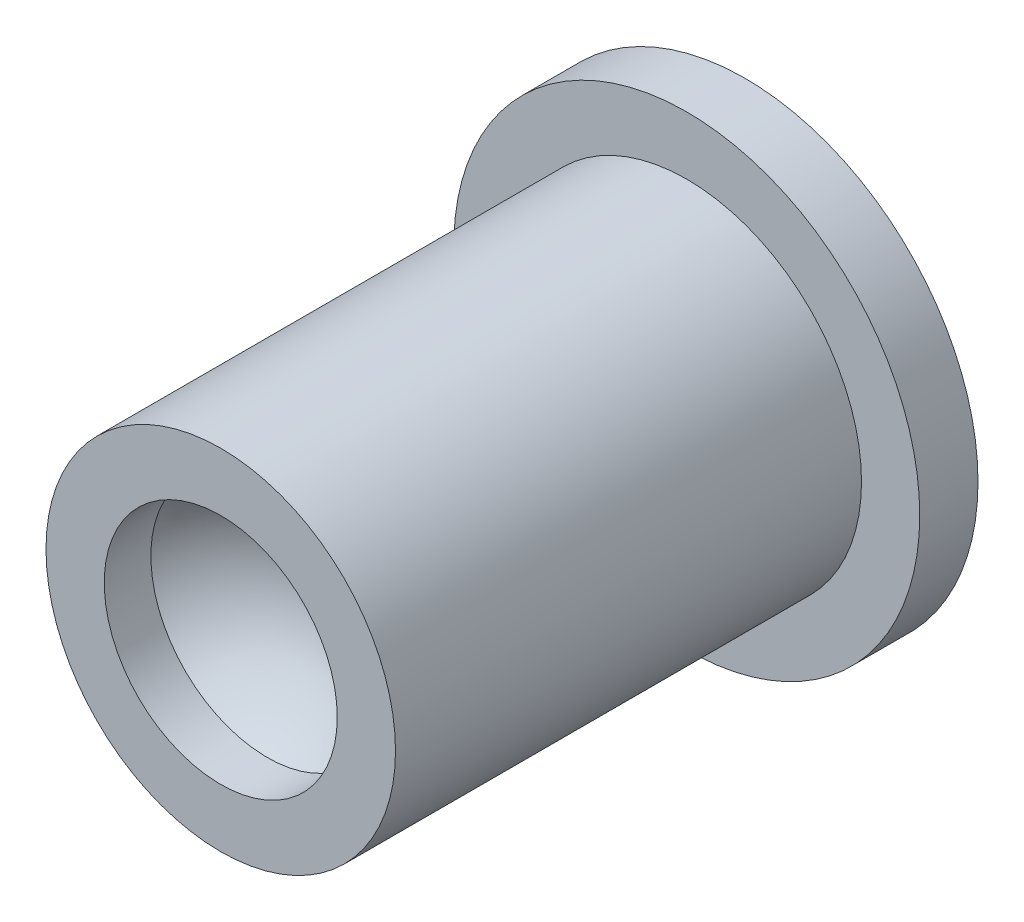
SolidWorks part; units mm, degrees
ref_plane "Front Plane" through (0, 0, 0) normal (0, 0, 1) x (1, 0, 0)
ref_plane "Top Plane" through (0, 0, 0) normal (0, 1, 0) x (1, 0, 0)
ref_plane "Right Plane" through (0, 0, 0) normal (1, 0, 0) x (0, 0, -1)
sketch "Sketch2" plane through (0, 0, 0) normal (0, 0, 1) x (1, 0, 0)
  circle A0 centre (0, 0) radius 4
  dimension "D1" = 8
extrude "Boss-Extrude1" add sketch "Sketch2" along normal blind 1
sketch "Sketch3" plane through (0, 0, 1) normal (0, 0, 1) x (1, 0, 0)
  circle A0 centre (0, 0) radius 3
extrude "Boss-Extrude2" add sketch "Sketch3" along normal blind 8
sketch "Sketch4" plane through (0, 0, 9) normal (0, 0, 1) x (1, 0, 0)
  circle A0 centre (0, 0) radius 2
extrude "Cut-Extrude4" cut sketch "Sketch4" against normal blind 0.8
dome "Dome2" faces to dome 1 distance 1 reverse direction yes elliptical dome no face at (2, 0, 8.2) parameters "D1"=1
